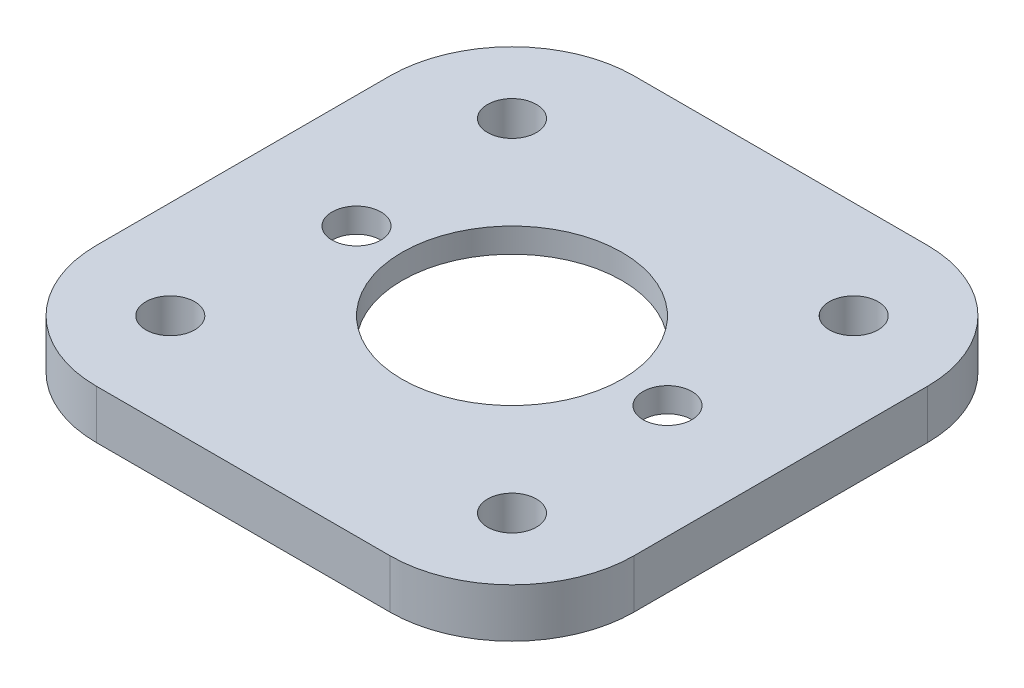
SolidWorks part; units mm, degrees
ref_plane "Front Plane" through (0, 0, 0) normal (0, 0, 1) x (1, 0, 0)
ref_plane "Top Plane" through (0, 0, 0) normal (0, 1, 0) x (1, 0, 0)
ref_plane "Right Plane" through (0, 0, 0) normal (1, 0, 0) x (0, 0, -1)
sketch "Sketch1" plane through (0, 0, 0) normal (0, 1, 0) x (1, 0, 0)
  line L1 (-6, 11) -> (6, 11)
  line L2 (-11, 6) -> (-11, -6)
  line L3 (-6, -11) -> (6, -11)
  line L4 (11, 6) -> (11, -6)
  line L5 (-11, 11) -> (11, -11) construction
  line L6 (-11, -11) -> (11, 11) construction
  line L7 (2.1213, 9.1924) -> (9.1924, 2.1213)
  line L8 (-2.1213, 9.1924) -> (-9.1924, 2.1213)
  line L9 (-9.1924, -2.1213) -> (-2.1213, -9.1924)
  line L10 (9.1924, -2.1213) -> (2.1213, -9.1924)
  line L11 (0, 11.3137) -> (0, -11.3137) construction
  line L12 (-11.3137, 0) -> (11.3137, 0) construction
  circle A0 centre (0, 0) radius 9.8885 construction
  circle A1 centre (-6.9922, 6.9922) radius 1
  circle A2 centre (6.9922, 6.9922) radius 1
  circle A3 centre (6.9922, -6.9922) radius 1
  circle A4 centre (-6.9922, -6.9922) radius 1
  arc A5 (-11, -6) -> (-6, -11) centre (-6, -6) ccw
  arc A6 (6, -11) -> (11, -6) centre (6, -6) ccw
  arc A7 (6, 11) -> (11, 6) centre (6, 6) cw
  arc A8 (-6, 11) -> (-11, 6) centre (-6, 6) ccw
  arc A9 (9.1924, 2.1213) -> (9.1924, -2.1213) centre (7.0711, 0) cw
  arc A10 (-2.1213, -9.1924) -> (2.1213, -9.1924) centre (0, -7.0711) ccw
  arc A11 (-9.1924, 2.1213) -> (-9.1924, -2.1213) centre (-7.0711, 0) ccw
  arc A12 (2.1213, 9.1924) -> (-2.1213, 9.1924) centre (0, 7.0711) ccw
  circle A13 centre (0, 0) radius 4.5
  circle A14 centre (-6.364, 0) radius 1
  circle A15 centre (6.364, 0) radius 1
  point P0 (0, 0)
  point P19 (0, 0)
  dimension "D2" = 19.777
  dimension "D3" = 2
  dimension "D7" = 5
  dimension "D8" = 3
  dimension "D9" = 9
  dimension "D10" = 2
  dimension "D1" = 22
  dimension "D5" = 45
  dimension "D6" = 16
  dimension "D4" = 4
extrude "Boss-Extrude1" add sketch "Sketch1" along normal blind 2 contours L1 A8 L2 A5 L3 A6 L4 A7 A12 L7 A9 L10 A10 L9 A11 L8 A1 A2 A3 A4 | L7 A12 L8 A11 L9 A10 L10 A9 A13 region at (0, 0, -10.6889) region at (5.4554, 0, -5.4554)
extrude "Cut-Extrude1" cut sketch "Sketch1<4>" along normal blind 1 contours L7 A12 L8 A11 L9 A10 L10 A9 A13 region at (5.4554, 0, -5.4554)
sketch "Sketch1<4>" plane through (0, 0, 0) normal (0, 1, 0) x (1, 0, 0) same geometry as "Sketch1"
